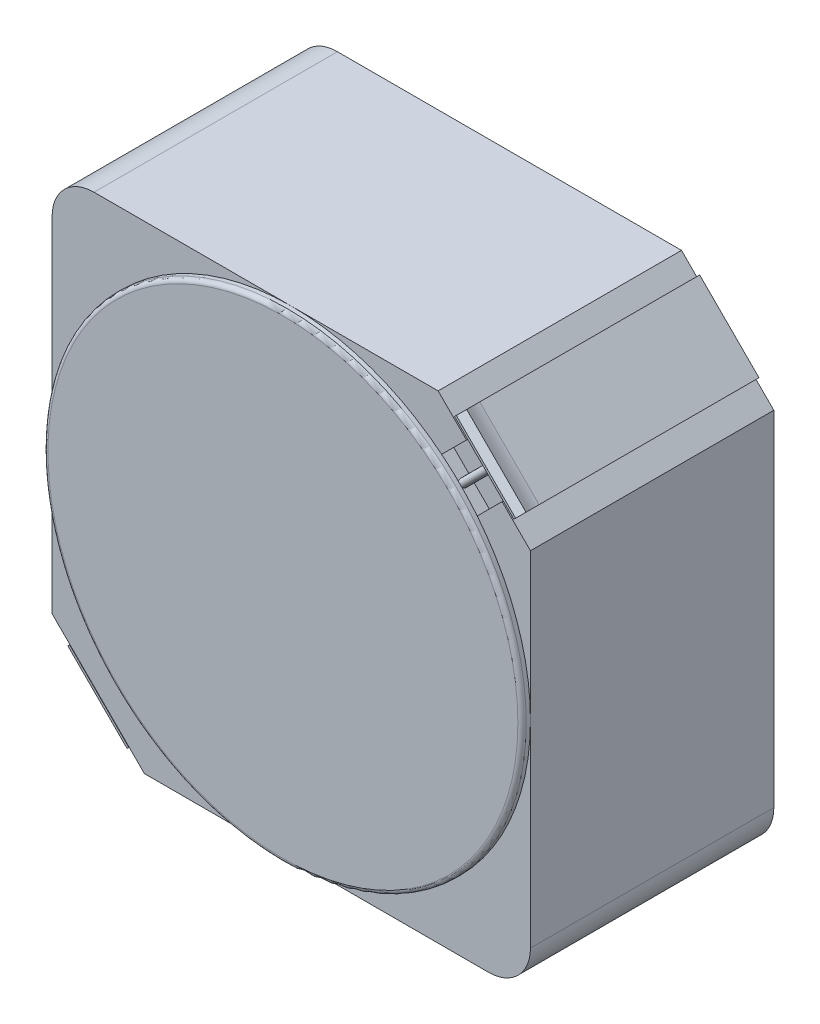
SolidWorks part; units mm, degrees
ref_plane "Спереди" through (0, 0, 0) normal (0, 0, 1) x (1, 0, 0)
ref_plane "Сверху" through (0, 0, 0) normal (0, 1, 0) x (1, 0, 0)
ref_plane "Справа" through (0, 0, 0) normal (1, 0, 0) x (0, 0, -1)
sketch "Эскиз1" plane through (0, 0, 0) normal (0, 0, 1) x (1, 0, 0)
  line L0 (-2.85, -1.75) -> (-1.75, -2.85)
  line L1 (-2.35, 2.85) -> (1.75, 2.85)
  line L2 (-2.85, 2.35) -> (-2.85, -1.75)
  line L3 (-1.75, -2.85) -> (2.35, -2.85)
  line L4 (2.85, 1.75) -> (2.85, -2.35)
  line L5 (-2.85, 2.85) -> (2.85, -2.85) construction
  line L6 (-2.85, -2.85) -> (2.85, 2.85) construction
  line L7 (1.75, 2.85) -> (2.85, 1.75)
  arc A0 (-2.35, 2.85) -> (-2.85, 2.35) centre (-2.35, 2.35) ccw
  arc A1 (2.35, -2.85) -> (2.85, -2.35) centre (2.35, -2.35) ccw
  point P0 (0, 0)
  dimension "D1" = 0.5
  dimension "D2" = 5.7
extrude "Корпус" add sketch "Эскиз1" along normal blind 2.9 from offset 0.005
sketch "Эскиз2" plane through (0, 0, 2.905) normal (0, 0, 1) x (1, 0, 0)
  line L0 (-2.85, 2.35) -> (-2.85, -1.75) construction
  circle A0 centre (0, 0) radius 2.85
extrude "Сердечник" add sketch "Эскиз2" along normal blind 0.1 and the other way blind 1
fillet "Скругление1" radius 0.05 1 edges at (2.85, 0, 3.005)
ref_plane "Плоскость1" through (0.55, -0.55, 0) normal (0.7071, -0.7071, 0) x (0, 0, 1)
sketch "Эскиз6" plane through (0.55, -0.55, 0) normal (0.7071, -0.7071, 0) x (0, 0, 1)
  line L0 (2.813, -3.3477) -> (2.9, -3.2957)
  line L1 (2.9, -3.2657) -> (0.03, -3.2657)
  line L2 (2.62, -3.2957) -> (0, -3.2957)
  line L3 (0, -3.2957) -> (0, -2.7657)
  line L4 (0.03, -3.2657) -> (0.03, -2.7657)
  line L5 (0.03, -2.7657) -> (0, -2.7657)
  line L6 (2.9, -3.2957) -> (2.9, -3.2657)
  line L8 (0.005, -3.2527) -> (2.905, -3.2527) construction
  line L9 (2.905, -2.85) -> (2.905, -2.0153) construction
  line L11 (0.005, 0.3536) -> (0.005, 3.2527) construction
  line L12 (2.905, -3.2527) -> (0.005, -3.2527) construction
  spline S0 degree 2 poles (2.62, -3.2957) (2.7238, -3.2995) (2.813, -3.3477) knots 0 0 0 1 1 1
  dimension "D2" = 0.5
  dimension "D3" = 0.013
  dimension "D4" = 0.025
  dimension "D5" = 0.005
  dimension "D6" = 0.082
  dimension "D7" = 0.087
  dimension "D8" = 120.867
  dimension "D9" = 0.28
  dimension "D10" = 0.1354
  dimension "D11" = 0.0295
  dimension "D12" = 0.03
extrude "вывод, бок" add sketch "Эскиз6" against normal blind 1 from offset 0.3 offset against normal yes
ref_point "Точка1"
ref_axis "Ось1" through (0, 0, 3.005) along (0, 0, -1)
sketch "Эскиз8" plane through (0, 0, 2.905) normal (0, 0, 1) x (1, 0, 0)
  line L0 (2.5121, 2.0879) -> (2.0879, 2.5121)
  line L2 (2.0879, 2.5121) -> (1.7357, 2.16)
  line L3 (-1.6879, -2.1121) -> (-1.3425, -1.7534)
  line L4 (1.9479, 1.9479) -> (0, 0) construction
  line L5 (2.5121, 2.0879) -> (2.16, 1.7357)
  line L6 (2.16, 1.7357) -> (1.7357, 2.16)
  line L7 (-1.7748, -1.3372) -> (-1.3425, -1.7534)
  line L8 (-2.1201, -1.696) -> (-1.7748, -1.3372)
  line L9 (-2.1201, -1.696) -> (-1.6879, -2.1121)
  line L10 (2.85, 1.75) -> (1.75, 2.85) construction
  dimension "D2" = 0.498
  dimension "D4" = 0.6
  dimension "D1" = 2
extrude "Вытянуть8" cut sketch "Эскиз8" against normal blind 0.2
sketch "Эскиз9" plane through (2.3092, 2.3092, 0) normal (-0.7071, -0.7071, 0) x (0, 0, 1)
  line L1 (0, 0) -> (2.804, 0) construction
  line L2 (2.9, 0.5222) -> (2.9, -0.4778) construction
  circle A0 centre (2.804, 0) radius 0.046
  dimension "D1" = 0.092
  dimension "D2" = 0.096
extrude "Бобышка-Вытянуть1" add sketch "Эскиз9" along normal up to next (0.511 mm away) and the other way blind 0.05 draft 45 from offset 0.05 other way draft outward yes
pattern_circular "Круговой массив3" count 2 over 360 about axis through (0, 0, 3.005) along (0, 0, -1) of "вывод, бок", "Бобышка-Вытянуть1"
sketch "Эскиз13" plane through (0, 0, 0.005) normal (0, 0, -1) x (-1, 0, 0)
  line L1 (-2.85, -2.35) -> (-2.85, 1.75) construction
  line L2 (0, -2.8) -> (0, 0) construction
  line L3 (2.85, 2.35) -> (2.85, -1.75) construction
  line L4 (1.9308, -2.6692) -> (1.75, -2.85) construction
  line L5 (1.6527, 0) -> (-1.6527, 0) construction
  line L6 (2.05, 1.1488) -> (2.8, 1.1488)
  line L7 (1.75, -2.85) -> (-2.35, -2.85) construction
  line L8 (2.8, 1.1488) -> (2.8, 1.7288)
  line L9 (1.7288, 2.8) -> (2.8, 1.7288)
  line L10 (-1.7288, 2.8) -> (1.7288, 2.8)
  line L11 (-2.8, 1.7288) -> (-1.7288, 2.8)
  line L12 (-2.8, -1.1488) -> (-2.05, -1.1488)
  line L13 (-2.8, -1.7288) -> (-2.8, -1.1488)
  line L16 (-2.8, -1.7288) -> (-1.7288, -2.8)
  line L17 (-2.8, 1.7288) -> (-2.8, 1.1488)
  line L18 (-1.7288, -2.8) -> (1.7288, -2.8)
  line L19 (1.7288, -2.8) -> (2.8, -1.7288)
  line L20 (2.8, -1.1488) -> (2.8, -1.7288)
  line L21 (2.05, -1.1488) -> (2.8, -1.1488)
  line L22 (-2.8, 1.1488) -> (-2.05, 1.1488)
  arc A0 (-2.05, -1.1488) -> (2.05, -1.1488) centre (0, 0) ccw
  arc A1 (-2.05, 1.1488) -> (2.05, 1.1488) centre (0, 0) cw
  circle A2 centre (0, 0) radius 2.85 construction
  dimension "D2" = 0.5
  dimension "D3" = 0.75
  dimension "D5" = 0.05
  dimension "D6" = 0.0503
  dimension "D7" = 0.05
  dimension "D1" = 0.58
extrude "Выводы низ" add sketch "Эскиз13" along normal up to surface (0.005 mm away) up to face at (-2.1273, -2.1587, 0)
